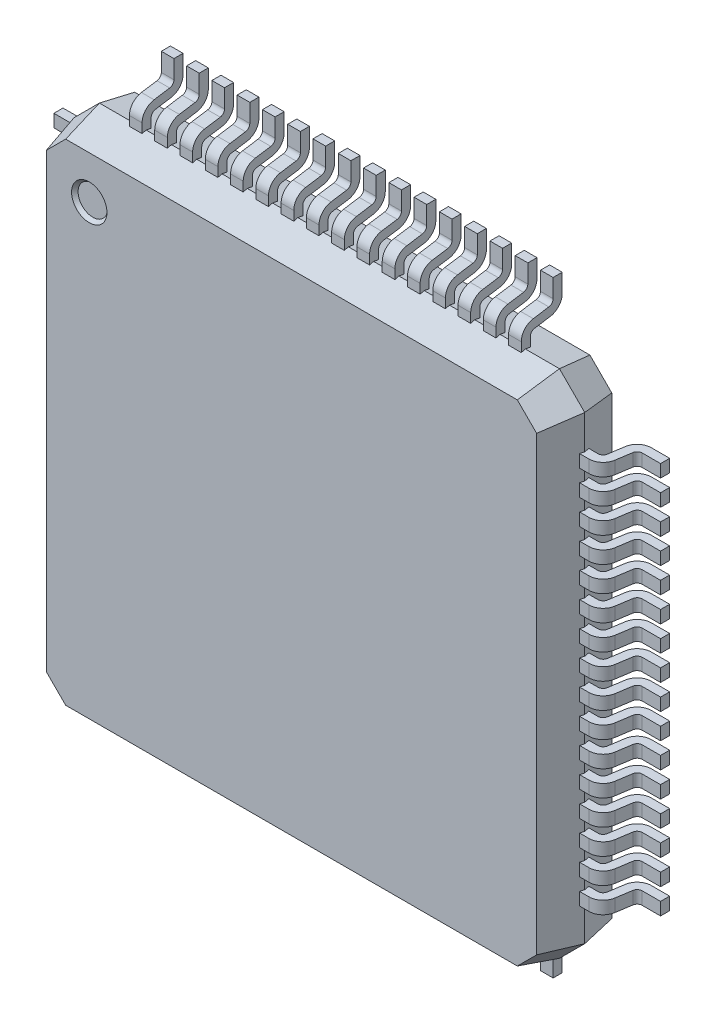
SolidWorks part; units mm, degrees
note: '?' marks a value the reader was unsure of.
ref_plane "Спереди" through (0, 0, 0) normal (0, 0, 1) x (1, 0, 0)
ref_plane "Сверху" through (0, 0, 0) normal (0, 1, 0) x (1, 0, 0)
ref_plane "Справа" through (0, 0, 0) normal (1, 0, 0) x (0, 0, -1)
sketch "Эскиз1" plane through (0, 0, 0) normal (0, 0, 1) x (1, 0, 0)
  line L0 (-5.05, 4.55) -> (-4.55, 5.05)
  line L1 (-4.55, 5.05) -> (4.55, 5.05)
  line L2 (-5.05, 4.55) -> (-5.05, -4.55)
  line L3 (-4.55, -5.05) -> (4.55, -5.05)
  line L4 (5.05, 4.55) -> (5.05, -4.55)
  line L5 (4.55, 5.05) -> (5.05, 4.55)
  line L6 (4.55, -5.05) -> (5.05, -4.55)
  line L7 (-5.05, -4.55) -> (-4.55, -5.05)
extrude "Вытянуть1" add sketch "Эскиз1" along normal blind 0.75 draft 15 and the other way blind 0.65 draft 10 from offset 0.75
sketch "Эскиз2" plane through (0, 0, 1.5) normal (0, 0, 1) x (1, 0, 0)
  circle A0 centre (-4, 4) radius 0.35
sketch "Эскиз3" plane through (0, 0, 0) normal (0, 1, 0) x (1, 0, 0)
  line L0 (5.3127, -0.5656) -> (5.3603, -0.2572)
  line L1 (5.6371, -0.02) -> (6, -0.02)
  line L2 (5.6371, -0.2) -> (6, -0.2)
  line L3 (5.5382, -0.2847) -> (5.4906, -0.5931)
  line L4 (4.9852, -0.8303) -> (5.2139, -0.8303)
  line L5 (0, 0) -> (0, -2) construction
  line L6 (-4.9852, -0.6503) -> (-5.2139, -0.6503)
  line L7 (-4.9852, -0.6503) -> (-4.9852, -0.8303)
  line L8 (-6, -0.02) -> (-6, -0.2)
  line L9 (-4.9852, -0.8303) -> (-5.2139, -0.8303)
  line L10 (-5.5382, -0.2847) -> (-5.4906, -0.5931)
  line L11 (-5.6371, -0.2) -> (-6, -0.2)
  line L12 (6, -0.02) -> (6, -0.2)
  line L13 (-5.6371, -0.02) -> (-6, -0.02)
  line L14 (4.9852, -0.6503) -> (4.9852, -0.8303)
  line L15 (-5.3127, -0.5656) -> (-5.3603, -0.2572)
  line L16 (4.9852, -0.6503) -> (5.2139, -0.6503)
  arc A0 (5.3603, -0.2572) -> (5.6371, -0.02) centre (5.6371, -0.3) cw
  arc A1 (5.4906, -0.5931) -> (5.2139, -0.8303) centre (5.2139, -0.5503) cw
  arc A2 (5.3127, -0.5656) -> (5.2139, -0.6503) centre (5.2139, -0.5503) cw
  arc A3 (5.5382, -0.2847) -> (5.6371, -0.2) centre (5.6371, -0.3) cw
  arc A4 (-5.5382, -0.2847) -> (-5.6371, -0.2) centre (-5.6371, -0.3) ccw
  arc A5 (-5.3127, -0.5656) -> (-5.2139, -0.6503) centre (-5.2139, -0.5503) ccw
  arc A6 (-5.4906, -0.5931) -> (-5.2139, -0.8303) centre (-5.2139, -0.5503) ccw
  arc A7 (-5.3603, -0.2572) -> (-5.6371, -0.02) centre (-5.6371, -0.3) ccw
extrude "Вытянуть2" add sketch "Эскиз3" against normal blind 0.25 from offset 3.875 separate body
extrude "Вытянуть3" cut sketch "Эскиз2" against normal blind 0.07 draft 40
pattern_linear "Линейный массив1" count 16 spacing 0.5 along (0, -1, 0) of "Вытянуть2"
ref_point "Точка1"
ref_axis "Ось1" through (0, 0, 0.1) along (0, 0, -1)?
pattern_circular "Круговой массив1" count 2 every 90 about axis through (0, 0, 0) along (0, 0, 1) of "Линейный массив1", "Вытянуть2"
